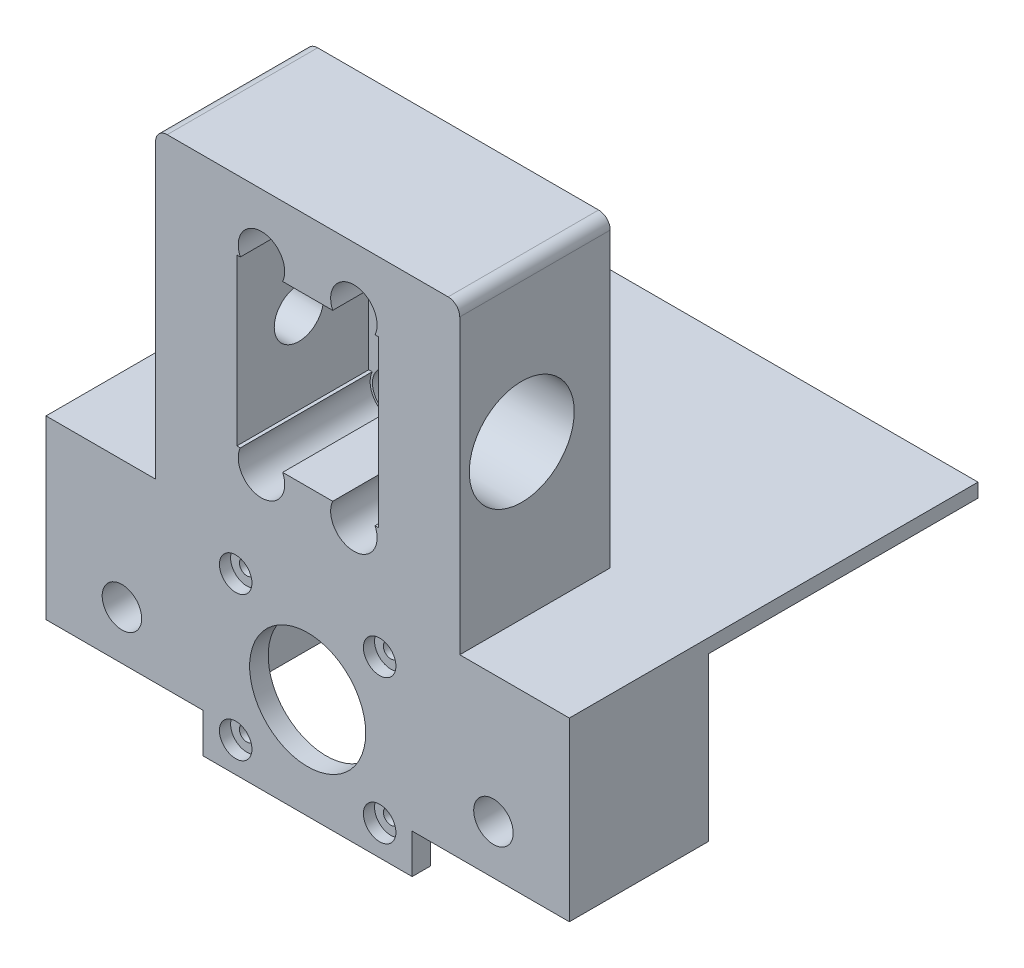
SolidWorks part; units mm, degrees
ref_plane "Front Plane" through (0, 0, 0) normal (0, 0, 1) x (1, 0, 0)
ref_plane "Top Plane" through (0, 0, 0) normal (0, 1, 0) x (1, 0, 0)
ref_plane "Right Plane" through (0, 0, 0) normal (1, 0, 0) x (0, 0, -1)
sketch "Sketch1" plane through (0, 0, 0) normal (0, 0, 1) x (1, 0, 0)
  line L1 (0, 0) -> (-65.5, 0)
  line L2 (0, 0) -> (0, -65.5)
  line L3 (0, -65.5) -> (-65.5, -65.5)
  line L4 (-65.5, 0) -> (-65.5, -65.5)
  line L5 (-17.5, -14.95) -> (-48, -14.95)
  line L6 (-17.5, -14.95) -> (-17.5, -50.55)
  line L7 (-17.5, -50.55) -> (-48, -50.55)
  line L8 (-48, -14.95) -> (-48, -50.55)
  point P10 (-32.75, -14.95)
  point P11 (-48, -32.75)
  point P12 (-65.5, -32.75)
  point P13 (-32.75, 0)
  dimension "D1" = 65.5
  dimension "D2" = 35.6
  dimension "D3" = 30.5
extrude "Boss-Extrude1" add sketch "Sketch1" along normal blind 28.4 and the other way blind 4
sketch "Sketch5" plane through (0, 0, 0) normal (1, 0, 0) x (0, 0, -1)
  line L2 (4, -65.5) -> (4, 0) construction
  line L4 (4, 0) -> (-28.4, 0) construction
  circle A1 centre (-15.05, -32.45) radius 11.3
  dimension "D1" = 11.3
  dimension "D2" = 19.05
  dimension "D3" = 32.45
extrude "Cut-Extrude1" cut sketch "Sketch5" against normal up to next
sketch "Sketch7" plane through (-65.5, 0, 0) normal (1, 0, 0) x (0, 0, -1)
  circle A1 centre (-15.05, -32.45) radius 5.3
  circle A3 centre (-15.05, -32.45) radius 11.3 construction
  circle A4 centre (-15.05, -32.45) radius 11.3 construction
  dimension "D1" = 5.3
extrude "Cut-Extrude4" cut sketch "Sketch7" along normal up to next
sketch "Sketch8" plane through (0, 0, -4) normal (0, 0, -1) x (-1, 0, 0)
  line L4 (17.5, -14.95) -> (17.5, -50.55)
  line L5 (48, -14.95) -> (17.5, -14.95)
  line L6 (48, -50.55) -> (48, -14.95)
  line L7 (17.5, -50.55) -> (48, -50.55)
  line L8 (17.5, -14.95) -> (17.5, -50.55)
  line L9 (48, -14.95) -> (17.5, -14.95)
  line L10 (48, -50.55) -> (48, -14.95)
  line L11 (17.5, -50.55) -> (48, -50.55)
  dimension "D2" = 30.5
  dimension "D3" = 35.6
  dimension "D1" = 0
extrude "Boss-Extrude2" add sketch "Sketch8" against normal blind 4
sketch "Sketch9" plane through (0, 0, -4) normal (0, 0, 1) x (1, 0, 0)
  line L0 (0, 0) -> (-65.5, 0) construction
  line L1 (0, 0) -> (0, -65.5) construction
  line L2 (0, -65.5) -> (-65.5, -65.5) construction
  line L3 (-32.75, -65.5) -> (-32.75, 0) construction
  line L4 (0, -32.75) -> (-65.5, -32.75) construction
  line L5 (-65.5, 0) -> (-65.5, -65.5) construction
  line L6 (-32.75, -65.5) -> (-32.75, -53.5) construction
  line L7 (-65.5, -65.5) -> (0, 0) construction
  circle A0 centre (-12.75, -12.9) radius 4.9
  circle A1 centre (-52.75, -12.9) radius 4.9
  circle A2 centre (-52.75, -52.6) radius 4.9
  circle A3 centre (-12.75, -52.6) radius 4.9
  point P20 (-32.75, -12)
  point P26 (-12, -32.75)
  point P27 (-53.5, -32.75)
  dimension "D3" = 9.8
  dimension "D1" = 12.9
  dimension "D2" = 12.75
  dimension "D4" = 12
extrude "Cut-Extrude5" cut sketch "Sketch9" along normal blind 2.2
fillet "Fillet1" radius 2.5 2 edges at (0, 0, 12.2) (-65.5, 0, 12.2)
sketch "Sketch10" plane through (0, 0, 0) normal (0, 0, 1) x (1, 0, 0)
  line L0 (0, -52.6) -> (-22.8, -52.6) construction
  line L1 (0, 0) -> (0, -65.5) construction
  line L2 (-22.8, -52.6) -> (-22.8, -65.5) construction
  line L3 (0, -65.5) -> (-65.5, -65.5) construction
  line L5 (-32.75, -65.5) -> (-32.75, 0) construction
  line L6 (0, -32.75) -> (-65.5, -32.75) construction
  line L7 (-32.75, -65.5) -> (-32.75, 0) construction
  line L8 (0, -32.75) -> (-65.5, -32.75) construction
  circle A0 centre (-22.8, -12.9) radius 5
  circle A1 centre (-42.7, -12.9) radius 5
  circle A2 centre (-22.8, -52.6) radius 5
  circle A3 centre (-42.7, -52.6) radius 5
  point P7 (-22.8, -12.9)
  point P8 (-42.7, -12.9)
  point P13 (-42.7, -52.6)
  dimension "D3" = 10
  dimension "D1" = 22.8
  dimension "D2" = 12.9
extrude "Cut-Extrude7" cut sketch "Sketch10" along normal up to next
sketch "Sketch20" plane through (0, 0, 0) normal (0, 0, 1) x (1, 0, 0)
  line L0 (-32.75, 0) -> (-32.75, -65.5) construction
  line L1 (-32.75, -65.5) -> (-32.75, 0) construction
  line L2 (-65.5, -32.75) -> (0, -32.75) construction
  line L3 (0, -32.75) -> (-65.5, -32.75) construction
  line L4 (-62.12, -65.5) -> (-3.38, -65.5) construction
  line L5 (0, -65.5) -> (-65.5, -65.5) construction
  line L6 (0, 0) -> (-65.5, 0) construction
  line L7 (0, 0) -> (0, -65.5) construction
  line L8 (-65.5, 0) -> (-65.5, -65.5) construction
  arc A0 (-38.1396, -14.95) -> (-47.2604, -14.95) centre (-42.7, -12.9) ccw construction
  point P0 (-42.7, -12.9)
  point P13 (-22.8, -12.9)
  point P15 (-22.8, -52.6)
  point P16 (-42.7, -52.6)
hole_wizard "CBORE for M4 Pan Head Machine Screw1" positions "3DSketch5" profile "Sketch22" counterbore size "M4" standard "ANSI Metric"
sketch3d "3DSketch5"
  point P0 (-42.7, -12.9, 0)
  point P3 (-22.8, -12.9, 0)
  point P6 (-42.7, -52.6, 0)
  point P9 (-22.8, -52.6, 0)
sketch "Sketch22" plane through (-42.7, -12.9, 0) normal (1, 0, 0) x (0, -1, 0)
  line L0 (0, 0) -> (0, 9.4421)
  line L1 (0, 9.4421) -> (2.4, 8)
  line L2 (2.4, 8) -> (2.4, 3.1)
  line L3 (2.4, 3.1) -> (4.5, 3.1)
  line L4 (4.5, 3.1) -> (4.5, 0)
  line L5 (4.5, 0) -> (0, 0)
  line L10 (0, 9.4421) -> (-2.4, 8) construction
  line L11 (0, -6.35) -> (0, 107.95) construction
  dimension "Hole Dia." = 4.8
  dimension "Hole Depth" = 8
  dimension "C'Bore Dia." = 9
  dimension "C'Bore Depth" = 3.1
  dimension "Drill Angle" = 118
sketch "Sketch23" plane through (0, -65.5, 0) normal (0, -1, 0) x (1, 0, 0)
  line L1 (23.6, 28.4) -> (-89.1, 28.4)
  line L2 (23.6, 28.4) -> (23.6, -59.6)
  line L3 (23.6, -59.6) -> (-89.1, -59.6)
  line L4 (-89.1, 28.4) -> (-89.1, -59.6)
  line L9 (-65.5, 28.4) -> (0, 28.4) construction
  point P4 (-32.75, -59.6)
  dimension "D1" = 88
  dimension "D2" = 112.7
extrude "Boss-Extrude3" add sketch "Sketch23" along normal blind 3
sketch "Sketch24" plane through (0, -68.5, 0) normal (0, -1, 0) x (-1, 0, 0)
  line L0 (-23.6, -28.4) -> (89.1, -28.4) construction
  line L1 (55.25, -28.4) -> (10.25, -28.4)
  line L2 (55.25, -28.4) -> (55.25, -24.4)
  line L3 (55.25, -24.4) -> (10.25, -24.4)
  line L4 (10.25, -28.4) -> (10.25, -24.4)
  point P6 (32.75, -28.4)
  dimension "D1" = 4
  dimension "D2" = 45
extrude "Boss-Extrude4" add sketch "Sketch24" along normal blind 43.5
sketch "Sketch25" plane through (0, 0, 28.4) normal (0, 0, 1) x (1, 0, 0)
  line L1 (-55.25, -68.5) -> (-89.1, -68.5) construction
  line L2 (-32.75, -112) -> (-32.75, 0) construction
  line L3 (-10.25, -112) -> (-55.25, -112) construction
  line L4 (-2.5, 0) -> (-63, 0) construction
  point P0 (-48.25, -74.5)
  point P5 (-48.25, -105.5)
  dimension "D1" = 15.5
  dimension "D2" = 6
  dimension "D3" = 31
sketch "Sketch28" plane through (0, 0, 28.4) normal (0, 0, 1) x (1, 0, 0)
  line L0 (-10.25, -112) -> (-55.25, -68.5) construction
  circle A0 centre (-32.75, -90.25) radius 22.0978
  circle A1 centre (-32.75, -90.25) radius 12.5
  dimension "D1" = 25
hole_wizard "CBORE for M3 Pan Head Machine Screw1" positions "Sketch26" profile "Sketch27" counterbore size "M3" standard "ANSI Metric" end condition up to next
sketch "Sketch26" plane through (0, 0, 28.4) normal (0, 0, 1) x (1, 0, 0)
  point P0 (-48.25, -74.5)
  point P4 (-48.25, -105.5)
sketch "Sketch27" plane through (-48.25, -74.5, 28.4) normal (1, 0, 0) x (0, -1, 0)
  line L0 (0, 0) -> (0, 4)
  line L1 (0, 4) -> (1.6, 4)
  line L3 (1.6, 4) -> (1.6, 2.4)
  line L4 (1.6, 2.4) -> (3.5, 2.4)
  line L5 (3.5, 2.4) -> (3.5, 0)
  line L7 (3.5, 0) -> (0, 0)
  line L11 (0, -6.35) -> (0, 107.95) construction
  dimension "Thru Hole Dia." = 3.2
  dimension "Thru Hole Depth" = 4
  dimension "C'Bore Dia." = 7
  dimension "C'Bore Depth" = 2.4
ref_plane "Plane1" through (-32.75, 0, 0) normal (1, 0, 0) x (0, 0, -1)
extrude "Cut-Extrude8" cut sketch "Sketch28" against normal up to next contours A1
mirror "Mirror1" about plane through (-32.75, 0, 0) normal (1, 0, 0) of "CBORE for M3 Pan Head Machine Screw1"
sketch "Sketch29" plane through (0, 0, 28.4) normal (0, 0, 1) x (1, 0, 0)
  line L0 (-32.75, -90) -> (-55.25, -90) construction
  line L1 (-55.25, -112) -> (-55.25, -68.5) construction
sketch "Sketch30" plane through (0, -68.5, 0) normal (0, -1, 0) x (-1, 0, 0)
  line L1 (55.25, -28.4) -> (89.1, -28.4)
  line L2 (55.25, -28.4) -> (55.25, 1.6)
  line L3 (55.25, 1.6) -> (89.1, 1.6)
  line L4 (89.1, -28.4) -> (89.1, 1.6)
  line L5 (89.1, -28.4) -> (89.1, 59.6) construction
  dimension "D1" = 30
extrude "Boss-Extrude5" add sketch "Sketch30" along normal blind 35
sketch "Sketch31" plane through (0, 0, 28.4) normal (0, 0, 1) x (1, 0, 0)
  line L0 (-72.75, -93) -> (-72.75, -103.5) construction
  line L1 (-55.25, -103.5) -> (-89.1, -103.5) construction
  circle A0 centre (-72.75, -93) radius 4.25
  dimension "D3" = 8.5
  dimension "D1" = 3
  dimension "D2" = 40
sketch "Sketch33" plane through (0, -103.5, 0) normal (0, -1, 0) x (-1, 0, 0)
  line L0 (72.75, -28.4) -> (72.75, 1.6) construction
  line L1 (89.1, 1.6) -> (55.25, 1.6) construction
  point P5 (72.75, -13.4)
  point P6 (72.75, -21.4)
  point P7 (72.75, -5.4)
  dimension "D1" = 8
  dimension "D2" = 8
extrude "Cut-Extrude10" cut sketch "Sketch31" against normal up to next
hole_wizard "CBORE for M3 Pan Head Machine Screw2" positions "Sketch34" profile "Sketch35" counterbore size "M3" standard "ANSI Metric" end condition up to next
sketch "Sketch34" plane through (0, -103.5, 0) normal (0, -1, 0) x (-1, 0, 0)
  point P0 (72.75, -13.4)
sketch "Sketch35" plane through (-72.75, -103.5, 13.4) normal (1, 0, 0) x (0, 0, -1)
  line L0 (0, 0) -> (0, 6.25)
  line L1 (0, 6.25) -> (1.6, 6.25)
  line L3 (1.6, 6.25) -> (1.6, 2.4)
  line L4 (1.6, 2.4) -> (3.5, 2.4)
  line L5 (3.5, 2.4) -> (3.5, 0)
  line L7 (3.5, 0) -> (0, 0)
  line L11 (0, -6.35) -> (0, 107.95) construction
  dimension "Thru Hole Dia." = 3.2
  dimension "Thru Hole Depth" = 6.25
  dimension "C'Bore Dia." = 7
  dimension "C'Bore Depth" = 2.4
mirror "Mirror2" about plane through (-32.75, 0, 0) normal (1, 0, 0) of "Cut-Extrude10", "CBORE for M3 Pan Head Machine Screw2", "Boss-Extrude5"
sketch "Sketch36" plane through (0, 0, 28.4) normal (0, 0, 1) x (1, 0, 0)
  circle A0 centre (-32.75, -90.25) radius 12.5 construction
  circle A1 centre (-72.75, -93) radius 4.25 construction
  point P0 (-32.75, -90.25)
  point P1 (-72.75, -93)
  point P2 (0, 0)
  point P5 (0, 0)
sketch "Sketch37" plane through (0, 0, 0) normal (1, 0, 0) x (0, 0, -1)
  point P0 (-13.2325, -17.6809)
